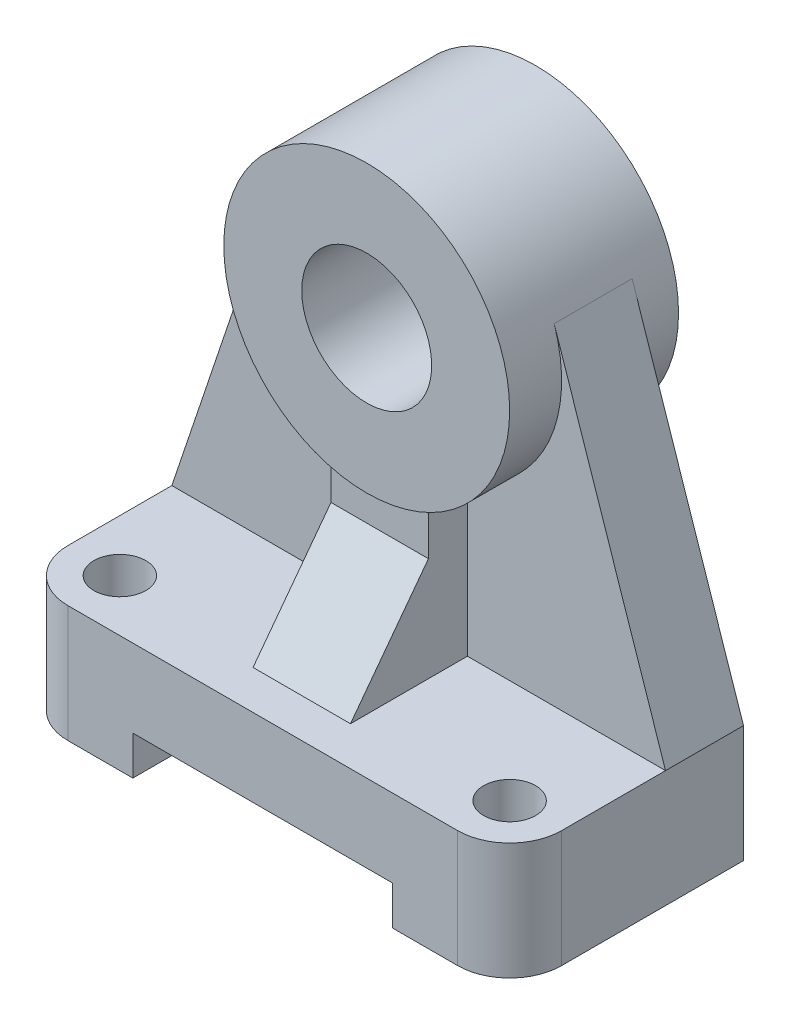
SolidWorks part; units mm, degrees
ref_plane "前视基准面" through (0, 0, 0) normal (0, 0, 1) x (1, 0, 0)
ref_plane "上视基准面" through (0, 0, 0) normal (0, 1, 0) x (1, 0, 0)
ref_plane "右视基准面" through (0, 0, 0) normal (1, 0, 0) x (0, 0, -1)
other "Configuration Table"
sketch "草图1" plane through (0, 0, 0) normal (0, 1, 0) x (1, 0, 0)
  line L1 (0, 0) -> (38, 0)
  line L2 (0, 0) -> (0, -14)
  line L3 (4, -18) -> (34, -18)
  line L4 (38, 0) -> (38, -14)
  arc A0 (34, -18) -> (38, -14) centre (34, -14) ccw
  arc A1 (0, -14) -> (4, -18) centre (4, -14) ccw
  circle A2 centre (4, -14) radius 2
  circle A3 centre (34, -14) radius 2
  point P9 (0, -18)
  dimension "D3" = 4
  dimension "D4" = 4
  dimension "D5" = 4
  dimension "D1" = 38
  dimension "D2" = 18
extrude "凸台-拉伸1" add sketch "草图1" along normal blind 9
sketch "草图3" plane through (0, 0, 0) normal (0, 0, -1) x (-1, 0, 0)
  line L0 (-22.5, 9) -> (-38, 9)
  line L1 (-19, 4.4718) -> (-19, 14.3836) construction
  line L2 (-22.5, 9) -> (-15.5, 9)
  line L3 (-38, 9) -> (-29.4267, 34.5049)
  line L5 (-15.5, 9) -> (0, 9)
  line L6 (0, 9) -> (-8.5733, 34.5049)
  circle A0 centre (-19, 31) radius 5
  circle A1 centre (-19, 31) radius 11
  point P7 (-19, 9)
  point P17 (-19, 9)
  line M9 (0, 9) -> (-38, 9)
  dimension "D1" = 22
  dimension "D2" = 10
  dimension "D3" = 22
  dimension "D4" = 7
extrude "凸台-拉伸2" add sketch "草图3" against normal blind 6 contours L2 L1 A1 L3 M9 | L1 L6 A1 M9 region at (19, 16.3215, 0)
extrude "凸台-拉伸4" add sketch "草图3<5>" along normal blind 3 and the other way blind 10 contours A1 L1 A0 | L1 A1 A0 region at (19, 41.6889, 0)
sketch "草图3<5>" plane through (0, 0, 0) normal (0, 0, -1) x (-1, 0, 0) same geometry as "草图3"
ref_plane "基准面2" through (19, 0, 0) normal (1, 0, 0) x (0, 0, -1)
sketch "草图6" plane through (19, 0, 0) normal (1, 0, 0) x (0, 0, -1)
  line L0 (-6, 9) -> (-15, 9)
  line L2 (-15, 9) -> (-9, 17)
  line L5 (-9, 17) -> (-9, 20)
  line L7 (-9, 20) -> (-6, 20)
  line L8 (-6, 20) -> (-6, 9)
  line L9 (-9, 17) -> (-6, 17)
  dimension "D2" = 9
  dimension "D3" = 8
extrude "凸台-拉伸14" add sketch "草图6" along normal mid plane 7.5 separate body contours L5 L9 L8 L7 | L9 L2 L0 L8 region at (19, 12.3333, 9.25) region at (19, 18.5, 7.5)
sketch "草图7" plane through (0, 0, 0) normal (0, 0, -1) x (-1, 0, 0)
  line L0 (-29, 0) -> (-9, 0)
  line L1 (-38, 0) -> (0, 0) construction
  line L2 (-9, 0) -> (-9, 3)
  line L3 (-9, 3) -> (-29, 3)
  line L4 (-19, 58.8839) -> (-19, -58.8839) construction
  line L5 (-29, 0) -> (-29, 3)
  point P9 (-19, 0)
  point P10 (-19, 3)
  dimension "D1" = 10
  dimension "D2" = 3
extrude "切除-拉伸1" cut sketch "草图7" against normal up to next (18 mm away) contours L0 L2 L3 L5
sketch "草图8" plane through (0, 20, 0) normal (0, 1, 0) x (1, 0, 0)
  line L12 (15.25, -6) -> (15.25, -9)
  line L13 (15.25, -9) -> (22.75, -9)
  line L14 (22.75, -9) -> (22.75, -6)
  line L15 (22.75, -6) -> (15.25, -6)
  line L16 (15.25, -6) -> (15.25, -9)
  line L17 (15.25, -9) -> (22.75, -9)
  line L18 (22.75, -9) -> (22.75, -6)
  line L19 (22.75, -6) -> (15.25, -6)
  dimension "D1" = 0
extrude "凸台-拉伸17" add sketch "草图8" along normal blind 4 separate body
